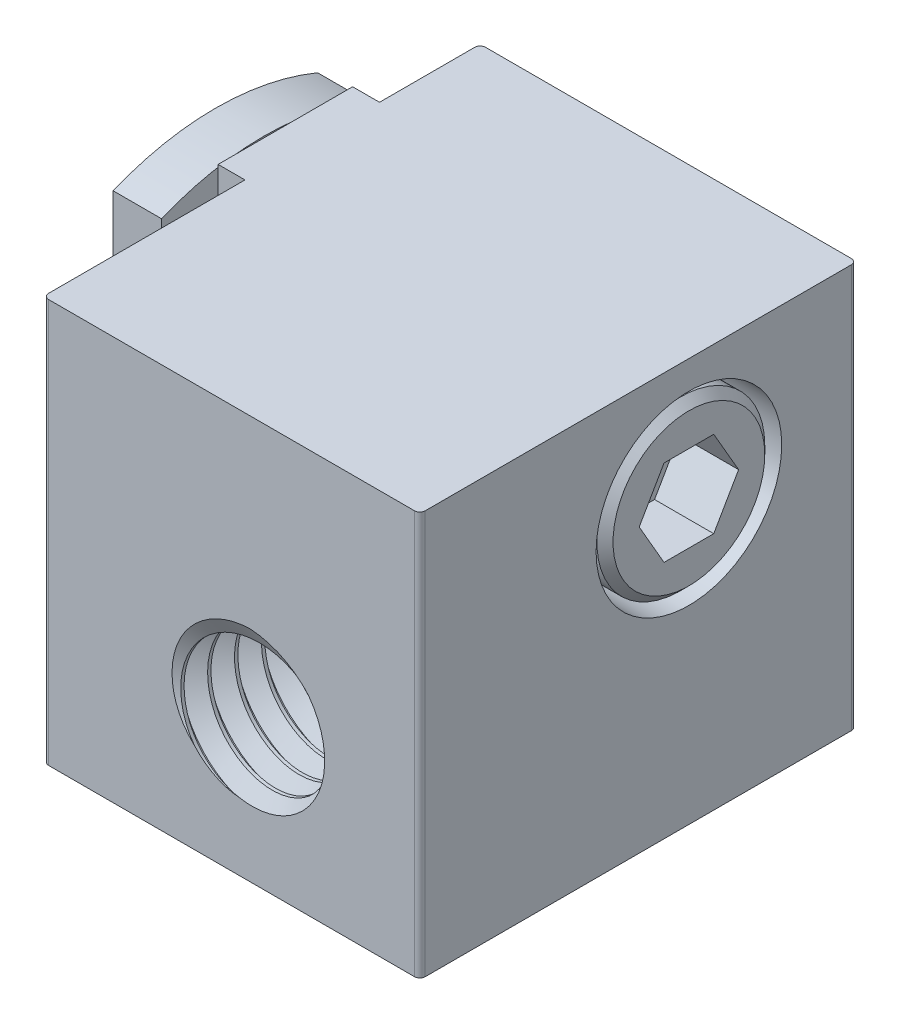
SolidWorks part; units mm, degrees
note: '?' marks a value the reader was unsure of.
other "Guide"
other "Main"
other "Screw" parameters "D1"=5.334, "Overall Height"=24.384, "Base Height"=28.9481, "Cutout Height"=1.27, "Tap Hole Diameter"=6.35, "Tap Hole Edge Distance"=8.255, "Tap Hole Bottom Distance"=6.35, "CB Depth"=5.334, "Rail Guide Height"=2.286, "D2"=24.384, "D3"=22.8222, "D4"=22.7434, "Screw Length"=24.384, "Length"=20.6248, "Width"=19.05, "Tab Length"=18.1102, "Tab Width"=6.35, "CB Diameter"=8.763, "Thru Hole Diameter"=5.1054, "CB Top Distance"=5.715, "CB Side Distance"=7.9248, "Rail Guide Width"=9.652, "Screw Head Dia"=7.9248, "Screw Dia"=4.7625, "Pitch"=1.27, "Rail Guide Length"=13.97
ref_plane "Front Plane" through (0, 0, 0) normal (0, 0, 1) x (1, 0, 0)
ref_plane "Top Plane" through (0, 0, 0) normal (0, 1, 0) x (1, 0, 0)
ref_plane "Right Plane" through (0, 0, 0) normal (1, 0, 0) x (0, 0, -1)
sketch "Sketch1" plane through (0, 0, 0) normal (1, 0, 0) x (0, 0, -1)
  line L0 (0, -9.525) -> (0, 9.525) construction
  line L1 (-10.3124, 0) -> (10.3124, 0) construction
  line L2 (2.3876, -16.2606) -> (2.3876, 23.8806) construction
  line L3 (-0.7874, 3.81) -> (5.5626, 3.81) construction
  line L4 (2.3876, -0.5715) -> (2.3876, 8.1915) construction
  line L5 (2.3876, 1.2573) -> (2.3876, 6.3627) construction
  line L6 (7.2136, 3.81) -> (-2.4384, 3.81) construction
  line L7 (6.35, 3.81) -> (-1.5748, 3.81) construction
  line L8 (2.3876, 6.1913) -> (2.3876, 1.4287) construction
  point P4 (0, 0)
  point P8 (0, 0)
  point P9 (0, 0)
  point P12 (2.3876, 3.81)
  point P15 (2.3876, 3.81)
  point P18 (2.3876, 3.81)
  point P21 (2.3876, 3.81)
  point P23 (2.3876, 3.81)
  point P26 (2.3876, 3.81)
  point P29 (2.3876, 3.81)
sketch "Sketch2" plane through (0, 0, 0) normal (0, 0, 1) x (1, 0, 0)
  line L0 (12.192, 0) -> (-12.192, 0) construction
  line L1 (12.192, 0) -> (-5.588, 0) construction
  line L2 (-5.588, 0) -> (-6.858, 0) construction
  line L3 (3.937, -6.35) -> (3.937, 0) construction
  line L4 (0, -9.525) -> (0, 9.525) construction
  line L5 (0, -9.525) -> (0, 9.525) construction
  line L6 (12.192, 0) -> (6.858, 0) construction
  line L7 (-7.874, 0) -> (-10.16, 0) construction
  line L8 (-10.16, 0) -> (-10.8915, 0) construction
  line L9 (-12.192, 0) -> (9.398, 0) construction
  line L10 (-12.192, 0) -> (12.192, 0) construction
  point P4 (0, 0)
  point P10 (3.937, -3.175)
  dimension "D1" = 1.016
  dimension "D2" = 0.7315
  dimension "D3" = 21.59
sketch "Sketch5" plane through (0, 0, 0) normal (0, 1, 0) x (1, 0, 0)
  line L8 (12.192, -10.3124) -> (12.192, 10.3124)
  line L9 (12.192, 10.3124) -> (-5.588, 10.3124)
  line L10 (-5.588, 10.3124) -> (-5.588, 5.5626)
  line L11 (-5.588, 5.5626) -> (-6.858, 5.5626)
  line L12 (-6.858, 5.5626) -> (-6.858, -0.7874)
  line L13 (-6.858, -0.7874) -> (-5.588, -0.7874)
  line L14 (-5.588, -0.7874) -> (-5.588, -10.3124)
  line L15 (-5.588, -10.3124) -> (12.192, -10.3124)
  point P7 (-6.858, 2.3876)
extrude "Main Body" add sketch "Sketch5" against normal up to vertex (9.525 mm away) and the other way up to vertex (9.525 mm away) up to point (0, -9.525, 0) other way up to point (0, 9.525, 0)
sketch "Sketch6" plane through (0, 0, 0) normal (0, 0, 1) x (1, 0, 0)
  circle A0 centre (3.937, -3.175) radius 3.175
extrude "Tap Hole" cut sketch "Sketch6" against normal through all both and the other way through all
sketch "Sketch10" plane through (0, 0, 0) normal (1, 0, 0) x (0, 0, -1)
  line L0 (7.2136, 7.62) -> (7.2136, -6.35)
  line L1 (-2.4384, 7.62) -> (-2.4384, -6.35)
  line L2 (-0.7874, 3.81) -> (5.5626, 3.81) construction
  arc A0 (7.2136, 7.62) -> (-2.4384, 7.62) centre (2.3876, -3.9899) ccw
  arc A3 (-2.4384, -6.35) -> (7.2136, -6.35) centre (2.3876, 5.2599) ccw
  dimension "D1" = 12.573
  dimension "D2" = 3.81
extrude "Rail Guide" add sketch "Sketch10" against normal up to vertex (10.16 mm away) from vertex at -7.874 separate body starting at point (-7.874, 0, 0)
sketch "Sketch11" plane through (-10.16, 0, 0) normal (-1, 0, 0) x (0, 0, 1)
  circle A0 centre (-2.3876, 3.81) radius 3.0632
  circle A1 centre (-2.3876, 3.81) radius 2.5527
  dimension "D1" = 6.1265
extrude "Boss-Extrude2" add sketch "Sketch11" along normal up to vertex (0.7315 mm away) up to point (-10.8915, 0, 0)
sketch "Sketch7" plane through (0, 0, 0) normal (1, 0, 0) x (0, 0, -1)
  circle A0 centre (2.3876, 3.81) radius 2.5527
extrude "Thru Hole" cut sketch "Sketch7" against normal through all both and the other way through all
sketch "Sketch8" plane through (0, 0, 0) normal (1, 0, 0) x (0, 0, -1)
  circle A0 centre (2.3876, 3.81) radius 4.3815
extrude "Counterbore" cut sketch "Sketch8" against normal blind 5.334 from surface at 12.192 starting at face at (12.192, 3.81, -4.9403)
sketch "Sketch12" plane through (0, 0, 0) normal (1, 0, 0) x (0, 0, -1)
  circle A0 centre (2.3876, 3.81) radius 2.5527
extrude "Screw Shaft" add sketch "Sketch12" against normal up to vertex (12.192 mm away) and the other way up to vertex (9.398 mm away) separate body up to point (-12.192, 0, 0) other way up to point (9.398, 0, 0)
sketch "Sketch13" plane through (9.398, 0, 0) normal (1, 0, 0) x (0, 0, -1)
  circle A0 centre (2.3876, 3.81) radius 3.9624
extrude "Screw Head" add sketch "Sketch13" along normal up to vertex (2.794 mm away) separate body up to point (12.192, 0, 0)
sketch "Sketch14" plane through (12.192, 0, 0) normal (1, 0, 0) x (0, 0, -1)
  line L0 (-0.7874, 3.81) -> (5.5626, 3.81) construction
  line L1 (4.734, 3.81) -> (3.5608, 5.842)
  line L2 (3.5608, 5.842) -> (1.2144, 5.842)
  line L3 (1.2144, 5.842) -> (0.0412, 3.81)
  line L4 (0.0412, 3.81) -> (1.2144, 1.778)
  line L5 (1.2144, 1.778) -> (3.5608, 1.778)
  line L6 (3.5608, 1.778) -> (4.734, 3.81)
  circle A0 centre (2.3876, 3.81) radius 2.032 construction
  dimension "D1" = 4.064
extrude "Cut-Extrude1" cut sketch "Sketch14" against normal up to vertex (2.794 mm away) up to point (9.398, 0, 0)
combine bodies "Combine3" operation type add bodies to combine 116 114
fillet "Fillet1" radius 0.254 4 edges at (-5.588, 0, -10.3124) (12.192, 0, -10.3124) (-5.588, 0, 10.3124) (12.192, 0, 10.3124)
chamfer "Chamfer4" distance 0.381 angle 45 2 edges at (-12.192, 3.81, -4.9403) (12.192, 3.81, -6.35)
ref_point "Point1"
ref_plane "Plane1" through (0, -3.175, 0) normal (0, 1, 0) x (1, 0, 0)
ref_plane "Plane5" through (3.937, 0, 0) normal (1, 0, 0) x (0, 0, -1)
sketch "Sketch16" plane through (0, 0, -10.3124) normal (0, 0, -1) x (-1, 0, 0)
  circle A0 centre (-3.937, -3.175) radius 3.175 construction
  circle A1 centre (-3.937, -3.175) radius 3.175
curve "Helix/Spiral1" pitch 1.27 height 21.8948 turns 17.24
sketch "Sketch15" plane through (0, -3.175, 0) normal (0, 1, 0) x (1, 0, 0)
  line L0 (0.8995, 11.503) -> (0.8995, 10.233) construction
  line L1 (0.8995, 10.233) -> (-0.2004, 10.868) construction
  line L2 (-0.2004, 10.868) -> (0.8995, 11.503) construction
  line L3 (-0.0629, 10.9474) -> (-0.0629, 10.7887) construction
  line L4 (0.762, 11.4236) -> (0.762, 10.3124) construction
  line L5 (0.8307, 11.4633) -> (0.8307, 10.2727) construction
  line L6 (0.762, 10.868) -> (0.8995, 10.868) construction
  line L7 (-0.2004, 10.868) -> (-0.0629, 10.868) construction
  line L8 (7.112, 10.3124) -> (0.762, 10.3124) construction
  line L9 (-0.0629, 10.9474) -> (0.8307, 11.4633)
  line L10 (0.8307, 11.4633) -> (0.8307, 10.2727)
  line L11 (0.8307, 10.2727) -> (-0.0629, 10.7887)
  line L12 (-0.0629, 10.7887) -> (-0.0629, 10.9474)
  point P11 (0.8307, 10.868)
  dimension "D1" = 0.1588
sweep "Cut-Sweep4" cut profiles "Sketch15" path "Helix/Spiral1"
ref_plane "Contact Plane 1" through (0, 0, 10.3124) normal (0, 0, 1) x (1, 0, 0)
ref_plane "Contact Plane 2" through (0, 0, -10.3124) normal (0, 0, -1) x (-1, 0, 0)
ref_plane "Contact Plane 3" through (-5.588, 0, 0) normal (-1, 0, 0) x (0, 0, 1)
ref_axis "Center Axis 1" through (3.937, -3.175, 17.4625) along (0, 0, -1)?
equation "\"D1@Counterbore\" = \"CB Depth@Sketch2\""
equation "\"D1@Sketch11\"=\"Thru Hole Diameter@Sketch1\"*1.2"
equation "\"D2@Sketch2\"=\"Screw Length@Sketch2\"*.03"
equation "\"D1@Sketch15\"=\"Pitch@Sketch15\"/8"
equation "\"D4@Helix/Spiral1\"=\"Pitch@Sketch15\""
equation "\"D3@Helix/Spiral1\"=\"D4@Helix/Spiral1\"+\"Length@Sketch1\""
equation "\"D1@Sketch10\"=\"Rail Guide Length@Sketch10\"*.9"
